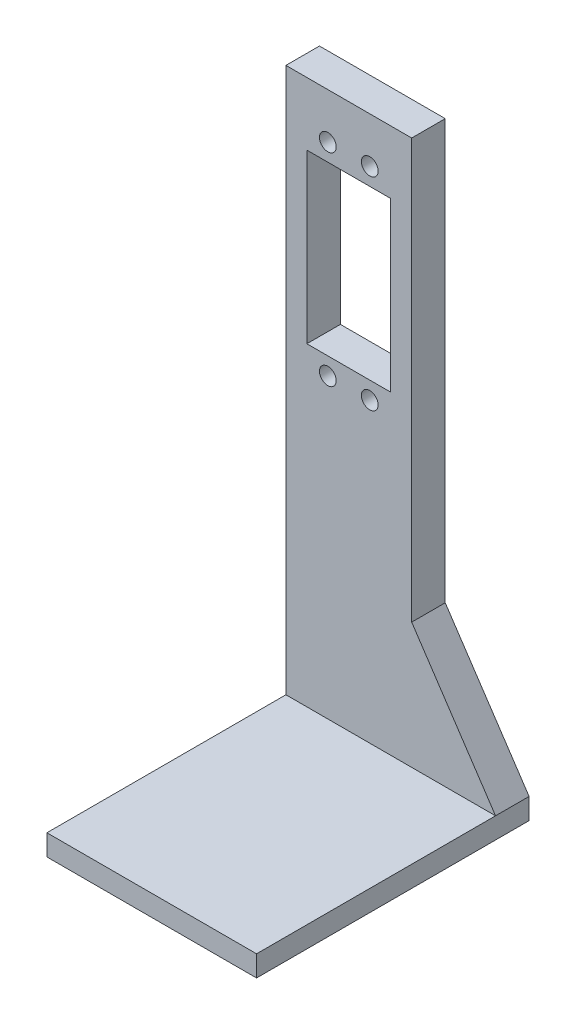
SolidWorks part; units mm, degrees
ref_plane "Front Plane" through (0, 0, 0) normal (0, 0, 1) x (1, 0, 0)
ref_plane "Top Plane" through (0, 0, 0) normal (0, 1, 0) x (1, 0, 0)
ref_plane "Right Plane" through (0, 0, 0) normal (1, 0, 0) x (0, 0, -1)
sketch "Sketch1" plane through (0, 0, 0) normal (0, 1, 0) x (1, 0, 0)
  line L0 (-50, 0) -> (-50, -65)
  line L1 (0, 0) -> (-50, 0)
  line L2 (0, 0) -> (0, -65)
  line L3 (0, -65) -> (-50, -65)
  dimension "D1" = 65
  dimension "D2" = 50
extrude "Boss-Extrude1" add sketch "Sketch1" along normal blind 5
sketch "Sketch2" plane through (0, 0, 0) normal (0, 0, 1) x (1, 0, 0)
  line L0 (0, 5) -> (-20, 35)
  line L1 (-20, 35) -> (-20, 135)
  line L2 (-20, 135) -> (-50, 135)
  line L3 (0, 5) -> (-50, 5)
  line L4 (-50, 5) -> (-50, 135)
  line L5 (0, 5) -> (-50, 5)
  dimension "D1" = 130
  dimension "D2" = 100
  dimension "D3" = 30
  dimension "D4" = 50
extrude "Boss-Extrude2" add sketch "Sketch2" along normal blind 8 contours L2 L4 L3 L0 L1
sketch "Sketch3" plane through (0, 0, 8) normal (0, 0, 1) x (1, 0, 0)
  line L0 (-50, 5) -> (-50, 135) construction
  line L1 (-45, 120) -> (-25, 120)
  line L2 (-45, 120) -> (-45, 80)
  line L3 (-45, 80) -> (-25, 80)
  line L4 (-25, 120) -> (-25, 80)
  line L5 (-20, 135) -> (-50, 135) construction
  circle A0 centre (-40, 124.15) radius 2
  circle A1 centre (-30, 124.15) radius 2
  circle A2 centre (-40, 75.85) radius 2
  circle A3 centre (-30, 75.85) radius 2
  dimension "D1" = 20
  dimension "D2" = 40
  dimension "D3" = 5
  dimension "D4" = 15
extrude "Cut-Extrude1" cut sketch "Sketch3" against normal through all
